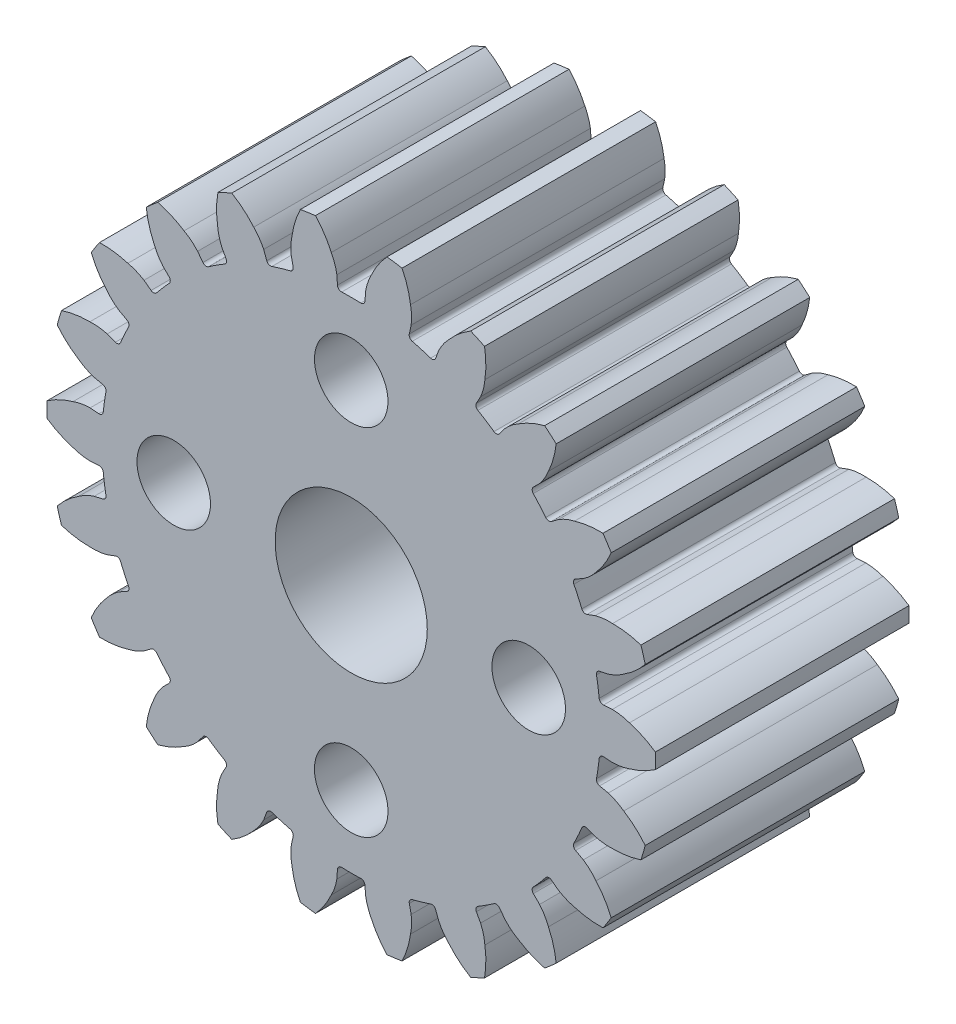
SolidWorks part; units mm, degrees
material "PVC 0.007 Plasticizado"
ref_plane "Plano frontal" through (0, 0, 0) normal (0, 0, 1) x (1, 0, 0)
ref_plane "Plano superior" through (0, 0, 0) normal (0, 1, 0) x (1, 0, 0)
ref_plane "Plano direito" through (0, 0, 0) normal (1, 0, 0) x (0, 0, -1)
sketch "Esboço1" plane through (0, 0, 0) normal (0, 0, 1) x (1, 0, 0)
  circle A108 centre (0, 0) radius 12
  dimension "D1" = 24
extrude "Ressalto-extrusão1" add sketch "Esboço1" along normal mid plane 10
sketch "Esboço2" plane through (0, 0, 5) normal (0, 0, 1) x (1, 0, 0)
  line L0 (0, 0) -> (0, 9.833) construction
  line L1 (0, 0) -> (0.7846, 10.972) construction
  line L2 (0, 0) -> (-0.7846, 10.972) construction
  line L3 (-0.7846, 10.972) -> (0.7846, 10.972) construction
  line L4 (0.5674, 10.3211) -> (0.5426, 9.9742)
  line L5 (-0.5674, 10.3211) -> (-0.5426, 9.9742)
  line L6 (0, 0) -> (-1.4097, 11.9169) construction
  circle A0 centre (0, 0) radius 11 construction
  circle A1 centre (0, 0) radius 10.3367 construction
  arc A2 (0.3769, 9.8258) -> (-0.3769, 9.8258) centre (0, 0) ccw
  circle A3 centre (0, 0) radius 12 construction
  arc A4 (1.4097, 11.9169) -> (-1.4097, 11.9169) centre (0, 0) ccw
  arc A5 (0.7846, 10.972) -> (1.4097, 11.9169) centre (3.9692, 9.5443) cw
  arc A6 (0.7846, 10.972) -> (0.5674, 10.3211) centre (2.6028, 10.0036) ccw
  arc A7 (-0.7846, 10.972) -> (-0.5674, 10.3211) centre (-2.6028, 10.0036) cw
  arc A8 (-0.7846, 10.972) -> (-1.4097, 11.9169) centre (-3.9692, 9.5443) ccw
  arc A9 (0.5426, 9.9742) -> (0.3769, 9.8258) centre (0.383, 9.9857) cw
  arc A10 (-0.5426, 9.9742) -> (-0.3769, 9.8258) centre (-0.383, 9.9857) ccw
  point P19 (0.5315, 9.8186)
  point P22 (-0.5315, 9.8186)
  dimension "D1" = 22
  dimension "D2" = 20.6734
  dimension "D3" = 19.666
  dimension "D7" = 3.49
  dimension "D8" = 2.06
  dimension "D10" = 6.747
  dimension "D4" = 0.16
  dimension "D5" = 4.09
  dimension "D6" = 1.5691
  dimension "D9" = 4.09
extrude "Corte-extrusão1" cut sketch "Esboço2" against normal through all
pattern_circular "PadrãoCircular2" count 22 over 360 about axis through (0, 0, 5) along (0, 0, 1) of "Corte-extrusão1"
sketch "Esboço3" plane through (0, 0, 5) normal (0, 0, 1) x (1, 0, 0)
  line L0 (-7, 0) -> (7, 0) construction
  line L1 (0, 7) -> (0, -7) construction
  circle A0 centre (0, 0) radius 3
  circle A1 centre (0, 7) radius 1.45
  circle A2 centre (0, -7) radius 1.45
  circle A3 centre (-7, 0) radius 1.45
  circle A4 centre (7, 0) radius 1.45
  point P6 (0, 0)
  point P9 (0, 0)
  dimension "D1" = 6
  dimension "D4" = 2.9
  dimension "D5" = 2.9
  dimension "D2" = 14
  dimension "D3" = 14
extrude "Corte-extrusão3" cut sketch "Esboço3" against normal through all
sketch "Esboço4" plane through (0, 0, 0) normal (0, 0, 1) x (1, 0, 0)
  line L0 (0, 10) -> (0, 12.25) construction
  line L17 (1.2282, 12.25) -> (-1.2282, 12.25) construction
  line L18 (1.1803, 12.1184) -> (0.4332, 10.0658)
  line L19 (0.3392, 10) -> (-0.3392, 10)
  line L20 (-1.1803, 12.1184) -> (-0.4332, 10.0658)
  line L21 (0, 9.833) -> (0, 12.7293) construction
  line L22 (-0.7732, 11) -> (0.7732, 11) construction
  line L23 (-1.3682, 12.25) -> (-1.5708, 12.25)
  line L24 (-1.5708, 12.25) -> (-1.5708, 22.25)
  line L25 (-1.5708, 22.25) -> (1.5708, 22.25)
  line L26 (1.5708, 22.25) -> (1.5708, 12.25)
  line L27 (1.5708, 12.25) -> (1.3682, 12.25)
  circle A0 centre (0, 0) radius 11 construction
  arc A1 (-0.7846, 10.972) -> (-1.4097, 11.9169) centre (-3.9692, 9.5443) ccw construction
  arc A3 (-0.5674, 10.3211) -> (-0.7846, 10.972) centre (-2.6028, 10.0036) ccw construction
  arc A4 (-0.3392, 10) -> (-0.4332, 10.0658) centre (-0.3392, 10.1) cw
  arc A5 (0.4332, 10.0658) -> (0.3392, 10) centre (0.3392, 10.1) cw
  arc A6 (1.3682, 12.25) -> (1.1803, 12.1184) centre (1.3682, 12.05) ccw
  arc A7 (-1.3682, 12.25) -> (-1.1803, 12.1184) centre (-1.3682, 12.05) cw
  dimension "D7" = 0.1
  dimension "D8" = 0.2
  dimension "D1" = 1.25
  dimension "D2" = 1
  dimension "D3" = 20
  dimension "D4" = 3.5011
  dimension "D5" = 10
  dimension "D6" = 3.1416
extrude "Ressalto-extrusão2" add sketch "Esboço4" along normal mid plane 10 separate body
pattern_linear "Padrão linear6" count 32 spacing 3.14 along (1, 0, 0) of "Ressalto-extrusão2"
sketch "Esboço6" plane through (-1.5708, 0, 0) normal (-1, 0, 0) x (0, 0, 1)
  line L1 (-5, 22.25) -> (5, 22.25)
  line L2 (-5, 22.25) -> (-5, 12.25)
  line L3 (-5, 12.25) -> (5, 12.25)
  line L4 (5, 22.25) -> (5, 12.25)
extrude "Ressalto-extrusão4" add sketch "Esboço6" against normal blind 100
delete or keep bodies "Corpo-Excluir/Manter 1" type delete bodies bodies 296
ref_axis "eixo de rotação" through (0, 0, 5.5) along (0, 0, -1)
